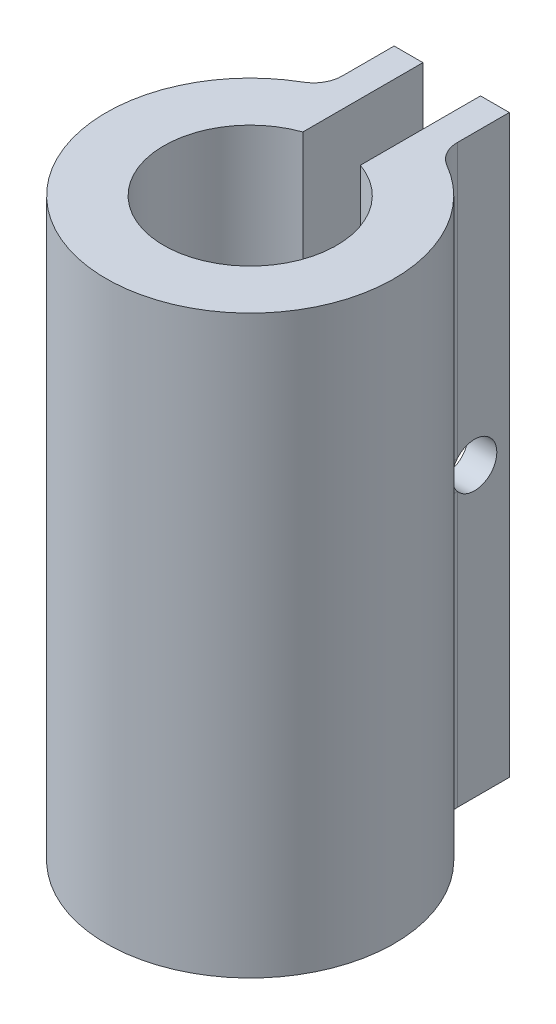
SolidWorks part; units mm, degrees
ref_plane "Front Plane" through (0, 0, 0) normal (0, 0, 1) x (1, 0, 0)
ref_plane "Top Plane" through (0, 0, 0) normal (0, 1, 0) x (1, 0, 0)
ref_plane "Right Plane" through (0, 0, 0) normal (1, 0, 0) x (0, 0, -1)
sketch "Sketch1" plane through (0, 0, 0) normal (0, 1, 0) x (1, 0, 0)
  line L0 (-2, 6) -> (-2, 14)
  line L1 (-4, 6) -> (4, 6)
  line L2 (-4, 6) -> (-4, 14)
  line L3 (-4, 14) -> (4, 14)
  line L4 (4, 6) -> (4, 14)
  line L5 (-4, 6) -> (4, 14) construction
  line L6 (-4, 14) -> (4, 6) construction
  line L7 (0, 44.1616) -> (0, 63.2064) construction
  line L8 (2, 6) -> (2, 14)
  line L9 (-2, 6) -> (-2, 3.4767)
  line L10 (2, 6) -> (2, 3.4767)
  circle A0 centre (0, 0) radius 6
  circle A1 centre (0, 0) radius 10
  point P5 (0, 10)
  dimension "D1" = 12
  dimension "D2" = 4
  dimension "D3" = 2
extrude "Boss-Extrude4" add sketch "Sketch1" along normal blind 40 contours L2 A1 L4 L1 L10 A0 L9 | L4 A1 L8 L1 | L0 A1 L2 L1 | A1 L0 L3 L2 | A1 L4 L3 L8 region at (-2.9701, 0, -7.7648) region at (-2.277, 0, -5.8284) region at (-3.0235, 0, -11.7563) region at (2.9701, 0, -7.7648) region at (3.0235, 0, -11.7563)
sketch "Sketch2" plane through (4, 0, 0) normal (1, 0, 0) x (0, 0, -1)
  line L0 (11.5826, 40) -> (11.5826, 0)
  line L1 (9.1652, 40) -> (14, 40) construction
  line L2 (9.1652, 0) -> (14, 0) construction
  circle A0 centre (11.5826, 20) radius 1.55
  dimension "D1" = 3.1
extrude "Cut-Extrude1" cut sketch "Sketch2" against normal through all contours L0 A0 | L0 A0 region at (4, 20, -12.2404) region at (4, 20, -10.9247)
fillet "Fillet1" radius 2 2 edges at (4, 20, -9.1652) (-4, 20, -9.1652)
ref_axis "Axis1" through (0, 200.8937, 0) along (0, -1, 0)
